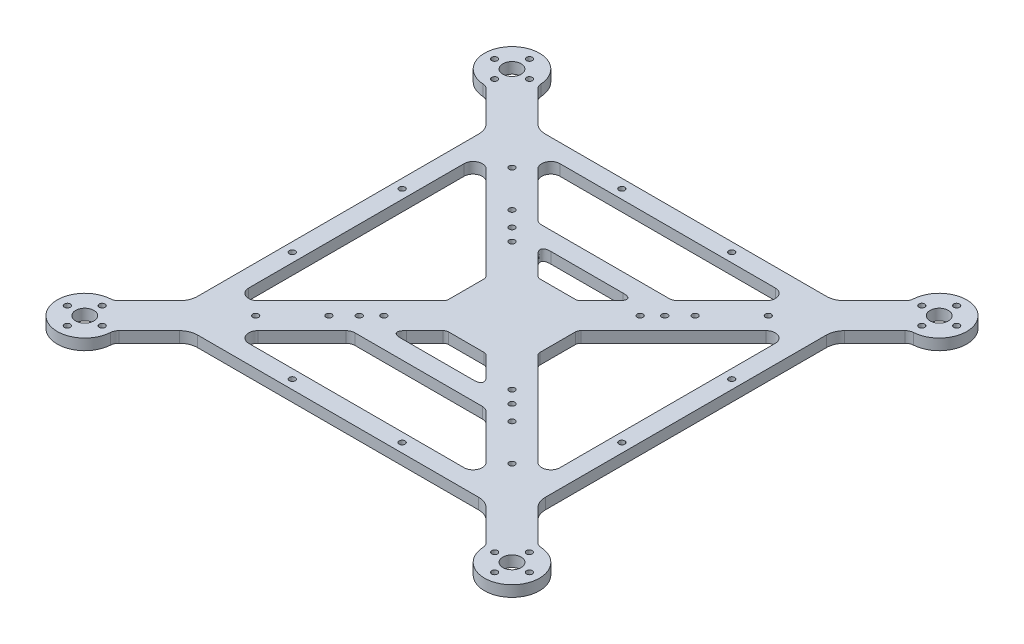
SolidWorks part; units mm, degrees
material "Thornel Mat VMA"
ref_plane "前视基准面" through (0, 0, 0) normal (0, 0, 1) x (1, 0, 0)
ref_plane "上视基准面" through (0, 0, 0) normal (0, 1, 0) x (1, 0, 0)
ref_plane "右视基准面" through (0, 0, 0) normal (1, 0, 0) x (0, 0, -1)
other "Configuration Table"
sketch "草图4" plane through (0, 0, 0) normal (0, 1, 0) x (1, 0, 0)
  line L0 (-115.838, 101.6959) -> (-97.9289, 83.7868)
  line L1 (-116.6726, -116.6726) -> (116.6726, -116.6726) construction
  line L2 (-116.6726, -116.6726) -> (-116.6726, 116.6726) construction
  line L3 (-116.6726, 116.6726) -> (116.6726, 116.6726) construction
  line L4 (116.6726, -116.6726) -> (116.6726, 116.6726) construction
  line L5 (-116.6726, -116.6726) -> (116.6726, 116.6726) construction
  line L6 (-116.6726, 116.6726) -> (116.6726, -116.6726) construction
  line L7 (-101.6959, 115.838) -> (-83.7868, 97.9289)
  line L8 (115.838, 101.6959) -> (97.9289, 83.7868)
  line L9 (101.6959, 115.838) -> (83.7868, 97.9289)
  line L10 (-95, 76.7157) -> (-95, -76.7157)
  line L11 (-85, 58.7868) -> (-85, -58.7868)
  line L12 (0, 0) -> (0, 141.074) construction
  line L13 (0, 0) -> (180.939, 0) construction
  line L14 (76.7157, 95) -> (-76.7157, 95)
  line L15 (58.7868, 85) -> (-58.7868, 85)
  line L16 (95, -76.7157) -> (95, 76.7157)
  line L17 (85, -58.7868) -> (85, 58.7868)
  line L18 (-76.7157, -95) -> (76.7157, -95)
  line L19 (-58.7868, -85) -> (58.7868, -85)
  line L20 (3.5355, -17.6777) -> (62.3223, -76.4645)
  line L21 (-62.3223, 76.4645) -> (-3.5355, 17.6777)
  line L22 (62.3223, 76.4645) -> (3.5355, 17.6777)
  line L23 (76.4645, 62.3223) -> (17.6777, 3.5355)
  line L24 (97.9289, -83.7868) -> (115.838, -101.6959)
  line L25 (83.7868, -97.9289) -> (101.6959, -115.838)
  line L26 (-83.7868, -97.9289) -> (-101.6959, -115.838)
  line L27 (-97.9289, -83.7868) -> (-115.838, -101.6959)
  line L28 (-17.6777, -3.5355) -> (-76.4645, -62.3223)
  line L29 (-3.5355, -17.6777) -> (-62.3223, -76.4645)
  line L30 (-76.4645, 62.3223) -> (-17.6777, 3.5355)
  line L31 (17.6777, -3.5355) -> (76.4645, -62.3223)
  circle A0 centre (-116.6726, 116.6726) radius 15
  circle A1 centre (-116.6726, 116.6726) radius 5
  circle A2 centre (-116.6726, 116.6726) radius 9.5 construction
  circle A3 centre (-116.6726, 126.1726) radius 1.6
  circle A4 centre (-107.1726, 116.6726) radius 1.6
  circle A5 centre (-116.6726, 107.1726) radius 1.6
  circle A6 centre (-126.1726, 116.6726) radius 1.6
  circle A7 centre (116.6726, 116.6726) radius 15
  circle A8 centre (116.6726, 116.6726) radius 5
  circle A9 centre (126.1726, 116.6726) radius 1.6
  circle A10 centre (116.6726, 107.1726) radius 1.6
  circle A11 centre (107.1726, 116.6726) radius 1.6
  circle A12 centre (116.6726, 126.1726) radius 1.6
  circle A13 centre (116.6726, 116.6726) radius 9.5 construction
  circle A14 centre (116.6726, -116.6726) radius 15
  circle A15 centre (116.6726, -116.6726) radius 5
  circle A16 centre (116.6726, -126.1726) radius 1.6
  circle A17 centre (107.1726, -116.6726) radius 1.6
  circle A18 centre (116.6726, -107.1726) radius 1.6
  circle A19 centre (126.1726, -116.6726) radius 1.6
  circle A20 centre (116.6726, -116.6726) radius 9.5 construction
  circle A21 centre (-116.6726, -116.6726) radius 15
  circle A22 centre (-116.6726, -116.6726) radius 5
  circle A23 centre (-126.1726, -116.6726) radius 1.6
  circle A24 centre (-116.6726, -107.1726) radius 1.6
  circle A25 centre (-107.1726, -116.6726) radius 1.6
  circle A26 centre (-116.6726, -126.1726) radius 1.6
  circle A27 centre (-116.6726, -116.6726) radius 9.5 construction
  arc A28 (-83.7868, 97.9289) -> (-76.7157, 95) centre (-76.7157, 105) ccw
  arc A29 (76.7157, 95) -> (83.7868, 97.9289) centre (76.7157, 105) ccw
  arc A30 (97.9289, 83.7868) -> (95, 76.7157) centre (105, 76.7157) ccw
  arc A31 (95, -76.7157) -> (97.9289, -83.7868) centre (105, -76.7157) ccw
  arc A32 (83.7868, -97.9289) -> (76.7157, -95) centre (76.7157, -105) ccw
  arc A33 (-76.7157, -95) -> (-83.7868, -97.9289) centre (-76.7157, -105) ccw
  arc A34 (-97.9289, -83.7868) -> (-95, -76.7157) centre (-105, -76.7157) ccw
  arc A35 (-95, 76.7157) -> (-97.9289, 83.7868) centre (-105, 76.7157) ccw
  arc A36 (-62.3223, -76.4645) -> (-58.7868, -85) centre (-58.7868, -80) ccw
  arc A37 (58.7868, -85) -> (62.3223, -76.4645) centre (58.7868, -80) ccw
  arc A38 (85, -58.7868) -> (76.4645, -62.3223) centre (80, -58.7868) cw
  arc A39 (76.4645, 62.3223) -> (85, 58.7868) centre (80, 58.7868) cw
  arc A40 (62.3223, 76.4645) -> (58.7868, 85) centre (58.7868, 80) ccw
  arc A41 (-62.3223, 76.4645) -> (-58.7868, 85) centre (-58.7868, 80) cw
  arc A42 (-76.4645, -62.3223) -> (-85, -58.7868) centre (-80, -58.7868) cw
  arc A43 (-85, 58.7868) -> (-76.4645, 62.3223) centre (-80, 58.7868) cw
  arc A44 (3.5355, -17.6777) -> (-3.5355, -17.6777) centre (0, -21.2132) ccw
  arc A45 (-17.6777, -3.5355) -> (-17.6777, 3.5355) centre (-21.2132, 0) ccw
  arc A46 (3.5355, 17.6777) -> (-3.5355, 17.6777) centre (0, 21.2132) cw
  arc A47 (17.6777, -3.5355) -> (17.6777, 3.5355) centre (21.2132, 0) cw
  point P0 (0, 0)
  point P20 (-116.6726, 116.6726)
  point P33 (116.6726, 116.6726)
  point P46 (116.6726, -116.6726)
  point P59 (-116.6726, -116.6726)
  point P60 (0, 0)
  point P69 (-95, 0)
  point P76 (-14.1421, 0)
  point P89 (0, 0)
  point P104 (-95, -80.8579)
  point P115 (85, 70.8579)
  point P118 (70.8579, 85)
  point P123 (-85, -70.8579)
  point P126 (-85, 70.8579)
  dimension "D2" = 30
  dimension "D3" = 10
  dimension "D4" = 19
  dimension "D5" = 3.2
  dimension "D14" = 10
  dimension "D15" = 5
  dimension "D16" = 5
  dimension "D17" = 5
  dimension "D18" = 5
  dimension "D19" = 5
  dimension "D1" = 330
  dimension "D8" = 20
  dimension "D9" = 20
  dimension "D10" = 10
  dimension "D11" = 190
  dimension "D12" = 190
  dimension "D13" = 10
  dimension "D6" = 4
  dimension "D7" = 4
extrude "凸台-拉伸2" add sketch "草图4" along normal blind 6 contours A35 L10 A34 L27 A21 L26 A33 L18 A32 L25 A14 L24 A31 L16 A30 L8 A7 L9 A29 L14 A28 L7 A0 L0 A45 L28 A42 L11 A43 L30 A44 L20 A37 L19 A36 L29 L22 A46 L21 A41 L15 A40 L31 A47 L23 A39 L17 | A0 A6 A5 A4 A3 A1 | A21 A26 A25 A24 A23 A22 | A14 A19 A18 A17 A16 A15 | A7 A12 A11 A10 A9 A8
sketch "草图6" plane through (0, 6, 0) normal (0, 1, 0) x (1, 0, 0)
  line L0 (-41, -26.8579) -> (-41, 26.8579)
  line L1 (-46, -29) -> (46, -29) construction
  line L2 (-46, -29) -> (-46, 29) construction
  line L3 (-46, 29) -> (46, 29) construction
  line L4 (46, -29) -> (46, 29) construction
  line L5 (-46, -29) -> (46, 29) construction
  line L6 (-46, 29) -> (46, -29) construction
  line L7 (-51, -36.8579) -> (-51, 36.8579)
  line L8 (-51, -29) -> (-51, 29) construction
  line L9 (-76.4645, 62.3223) -> (-17.6777, 3.5355) construction
  line L10 (-41, -29) -> (-41, 29) construction
  line L11 (-17.6777, -3.5355) -> (-76.4645, -62.3223) construction
  line L12 (-41, -26.8579) -> (-51, -36.8579)
  line L13 (-51, 36.8579) -> (-41, 26.8579)
  line L14 (0, 0) -> (0, 52.0097) construction
  line L15 (51, 36.8579) -> (41, 26.8579)
  line L16 (41, -26.8579) -> (51, -36.8579)
  line L17 (51, -36.8579) -> (51, 36.8579)
  line L18 (41, -26.8579) -> (41, 26.8579)
  line L19 (-26.8579, 41) -> (26.8579, 41)
  line L20 (25, -25) -> (-25, -25)
  line L21 (25, -25) -> (25, 25)
  line L22 (25, 25) -> (-25, 25)
  line L23 (-25, -25) -> (-25, 25)
  line L24 (25, -25) -> (-25, 25) construction
  line L25 (25, 25) -> (-25, -25) construction
  line L26 (-36.8579, 51) -> (36.8579, 51)
  line L27 (-26.8579, 41) -> (-36.8579, 51)
  line L28 (36.8579, 51) -> (26.8579, 41)
  line L29 (-29, 46) -> (29, 46) construction
  line L30 (36.8579, -51) -> (26.8579, -41)
  line L31 (-26.8579, -41) -> (-36.8579, -51)
  line L32 (-36.8579, -51) -> (36.8579, -51)
  line L33 (-26.8579, -41) -> (26.8579, -41)
  line L34 (-29, -46) -> (29, -46) construction
  line L35 (41, 26.8579) -> (41, -26.8579)
  line L36 (51, 36.8579) -> (51, -36.8579)
  line L37 (41, 26.8579) -> (51, 36.8579)
  line L38 (51, -36.8579) -> (41, -26.8579)
  line L39 (46, 29) -> (46, -29) construction
  line L40 (-51, -36.8579) -> (-41, -26.8579)
  line L41 (-41, 26.8579) -> (-51, 36.8579)
  line L42 (-51, 36.8579) -> (-51, -36.8579)
  line L43 (-41, 26.8579) -> (-41, -26.8579)
  line L44 (-46, 29) -> (-46, -29) construction
  line L45 (26.8579, -41) -> (-26.8579, -41)
  line L46 (36.8579, -51) -> (-36.8579, -51)
  line L47 (26.8579, -41) -> (36.8579, -51)
  line L48 (-36.8579, -51) -> (-26.8579, -41)
  line L49 (29, -46) -> (-29, -46) construction
  line L50 (-36.8579, 51) -> (-26.8579, 41)
  line L51 (26.8579, 41) -> (36.8579, 51)
  line L52 (36.8579, 51) -> (-36.8579, 51)
  line L53 (26.8579, 41) -> (-26.8579, 41)
  line L54 (29, 46) -> (-29, 46) construction
  point P0 (0, 0)
  point P67 (0, 0)
  dimension "D1" = 58
  dimension "D2" = 92
  dimension "D5" = 50
  dimension "D6" = 50
  dimension "D3" = 5
  dimension "D4" = 5
  dimension "D7" = 4
extrude "凸台-拉伸3" add sketch "草图6" against normal up to surface (6 mm away) contours L13 L7 L12 L0 | L18 L16 L17 L15 | L28 L26 L27 L19 | L33 L31 L32 L30 up to face at (-59.8637, 0, 0)
sketch "草图7" plane through (0, 6, 0) normal (0, 1, 0) x (1, 0, 0)
  line L1 (10, -10) -> (-10, -10) construction
  line L2 (10, -10) -> (10, 10) construction
  line L3 (10, 10) -> (-10, 10) construction
  line L4 (-10, -10) -> (-10, 10) construction
  line L5 (10, -10) -> (-10, 10) construction
  line L6 (10, 10) -> (-10, -10) construction
  line L7 (46, -29) -> (-46, -29) construction
  line L8 (46, -29) -> (46, 29) construction
  line L9 (46, 29) -> (-46, 29) construction
  line L10 (-46, -29) -> (-46, 29) construction
  line L11 (46, -29) -> (-46, 29) construction
  line L12 (46, 29) -> (-46, -29) construction
  circle A0 centre (-10, 10) radius 1.5
  circle A1 centre (10, 10) radius 1.5
  circle A2 centre (10, -10) radius 1.5
  circle A3 centre (-10, -10) radius 1.5
  circle A4 centre (-46, 29) radius 1.5
  circle A5 centre (46, 29) radius 1.5
  circle A6 centre (46, -29) radius 1.5
  circle A7 centre (-46, -29) radius 1.5
  point P0 (0, 0)
  point P2 (0, 0)
  point P16 (0, 0)
  dimension "D3" = 3
  dimension "D7" = 3
  dimension "D1" = 20
  dimension "D2" = 20
  dimension "D5" = 92
  dimension "D6" = 58
  dimension "D4" = 4
extrude "切除-拉伸1" [suppressed] cut sketch "草图7" against normal through all
fillet "圆角2" radius 3 8 edges at (41, 3, -26.8579) (41, 3, 26.8579) (-41, 3, 26.8579) (-41, 3, -26.8579) (26.8579, 3, 41) (-26.8579, 3, 41) (26.8579, 3, -41) (-26.8579, 3, -41)
fillet "圆角3" radius 5 8 edges at (51, 3, 36.8579) (51, 3, -36.8579) (-51, 3, 36.8579) (-51, 3, -36.8579) (-36.8579, 3, 51) (36.8579, 3, 51) (36.8579, 3, -51) (-36.8579, 3, -51)
fillet "圆角4" radius 5 8 edges at (101.6959, 3, -115.838) (115.838, 3, -101.6959) (115.838, 3, 101.6959) (101.6959, 3, 115.838) (-101.6959, 3, 115.838) (-115.838, 3, 101.6959) (-101.6959, 3, -115.838) (-115.838, 3, -101.6959)
sketch "草图8" plane through (0, 6, 0) normal (0, 1, 0) x (1, 0, 0)
  line L1 (20, -20) -> (-20, -20) construction
  line L2 (20, -20) -> (20, 20) construction
  line L3 (20, 20) -> (-20, 20) construction
  line L4 (-20, -20) -> (-20, 20) construction
  line L5 (20, -20) -> (-20, 20) construction
  line L6 (20, 20) -> (-20, -20) construction
  circle A0 centre (-20, 20) radius 1.5
  circle A1 centre (20, 20) radius 1.5
  circle A2 centre (20, -20) radius 1.5
  circle A3 centre (-20, -20) radius 1.5
  point P0 (0, 0)
  point P16 (0, 0)
  dimension "D3" = 3
  dimension "D1" = 40
  dimension "D2" = 40
  dimension "D4" = 4
extrude "切除-拉伸2" [suppressed] cut sketch "草图8" against normal through all
sketch "草图9" plane through (0, 6, 0) normal (0, 1, 0) x (1, 0, 0)
  line L1 (0, 0) -> (0, 15.1616) construction
  line L2 (0, 0) -> (18.0574, 0) construction
  line L3 (0, 0) -> (-35, 35) construction
  circle A0 centre (-35, 35) radius 1.6
  circle A3 centre (35, 35) radius 1.6
  circle A4 centre (-35, -35) radius 1.6
  circle A5 centre (35, -35) radius 1.6
  dimension "D2" = 3.2
  dimension "D1" = 45
  dimension "D3" = 70
extrude "切除-拉伸3" cut sketch "草图9" against normal through all
sketch "草图10" [suppressed] plane through (0, 6, 0) normal (0, 1, 0) x (1, 0, 0)
  circle A0 centre (-46, 29) radius 1.5 construction
  circle A1 centre (-46, 29) radius 1.5
  circle A2 centre (46, 29) radius 1.5 construction
  circle A3 centre (46, 29) radius 1.5
  circle A4 centre (-46, -29) radius 1.5 construction
  circle A5 centre (-46, -29) radius 1.5
  circle A6 centre (46, -29) radius 1.5 construction
  circle A7 centre (46, -29) radius 1.5
extrude "凸台-拉伸4" [suppressed] add sketch "草图10" against normal up to surface (6 mm away)
sketch "草图11" plane through (0, 6, 0) normal (0, 1, 0) x (1, 0, 0)
  line L1 (27.5, -27.5) -> (-27.5, -27.5) construction
  line L2 (27.5, -27.5) -> (27.5, 27.5) construction
  line L3 (27.5, 27.5) -> (-27.5, 27.5) construction
  line L4 (-27.5, -27.5) -> (-27.5, 27.5) construction
  line L5 (27.5, -27.5) -> (-27.5, 27.5) construction
  line L6 (27.5, 27.5) -> (-27.5, -27.5) construction
  circle A0 centre (-27.5, 27.5) radius 1.6
  circle A1 centre (27.5, 27.5) radius 1.6
  circle A2 centre (27.5, -27.5) radius 1.6
  circle A3 centre (-27.5, -27.5) radius 1.6
  point P0 (0, 0)
  point P16 (0, 0)
  dimension "D3" = 3.2
  dimension "D1" = 55
  dimension "D4" = 4
extrude "切除-拉伸4" [suppressed] cut sketch "草图11" against normal through all
sketch "草图12" plane through (0, 6, 0) normal (0, 1, 0) x (1, 0, 0)
  line L0 (-35.8787, 21.7365) -> (-52.4645, 38.3223)
  line L1 (-35.8787, -21.7365) -> (-52.4645, -38.3223)
  line L2 (-41, -19.6152) -> (-41, 19.6152) construction
  line L3 (-51, -34.7868) -> (-51, 34.7868) construction
  line L4 (-41, -19.6152) -> (-41, 19.6152)
  line L5 (-51, -34.7868) -> (-51, 34.7868)
  line L6 (0, 0) -> (0, 23.6826) construction
  line L7 (51, -34.7868) -> (51, 34.7868)
  line L8 (41, -19.6152) -> (41, 19.6152)
  line L9 (35.8787, -21.7365) -> (52.4645, -38.3223)
  line L10 (35.8787, 21.7365) -> (52.4645, 38.3223)
  arc A0 (-52.4645, -38.3223) -> (-51, -34.7868) centre (-56, -34.7868) ccw construction
  arc A1 (-51, 34.7868) -> (-52.4645, 38.3223) centre (-56, 34.7868) ccw construction
  arc A2 (-52.4645, -38.3223) -> (-51, -34.7868) centre (-56, -34.7868) ccw
  arc A3 (-51, 34.7868) -> (-52.4645, 38.3223) centre (-56, 34.7868) ccw
  arc A4 (51, 34.7868) -> (52.4645, 38.3223) centre (56, 34.7868) cw
  arc A5 (52.4645, -38.3223) -> (51, -34.7868) centre (56, -34.7868) cw
  spline S0 degree 2 poles (117.6067, -1974.0441) (-43.0823, -8.6989) (-40.9727, 20.7023) (-40.9301, 21.2952) (-40.8081, 21.7781) (-40.6594, 22.3663) (-40.4006, 22.7849) (-40.0718, 23.3164) (-39.6048, 23.5072) (-39.1393, 23.6973) (-38.5319, 23.5511) (-38.0543, 23.4362) (-37.5355, 23.1253) (-37.1113, 22.8711) (-36.6658, 22.4851) (-14.4014, 3.1962) (1261.9746, -1499.9408) knots -9.521184 -9.521184 -9.521184 0.125 0.125 0.25 0.25 0.375 0.375 0.5 0.5 0.625 0.625 0.75 0.75 0.875 0.875 10.526415 10.526415 10.526415 only from (-41, 19.6152) to (-35.8787, 21.7365) construction
  spline S1 degree 2 poles (1261.6995, 1500.1454) (-14.3852, -3.1878) (-36.6667, -22.4859) (-37.116, -22.875) (-37.5437, -23.1302) (-38.0648, -23.4411) (-38.5438, -23.554) (-39.1522, -23.6973) (-39.6173, -23.502) (-40.0809, -23.3073) (-40.407, -22.7744) (-40.6634, -22.3554) (-40.8105, -21.7687) (-40.9306, -21.2891) (-40.9728, -20.7011) (-43.0767, 8.6815) (117.2676, 1974.094) knots -9.521184 -9.521184 -9.521184 0.125 0.125 0.25 0.25 0.375 0.375 0.5 0.5 0.625 0.625 0.75 0.75 0.875 0.875 10.526415 10.526415 10.526415 only from (-35.8787, -21.7365) to (-41, -19.6152) construction
  spline S2 degree 2 poles (-41, 19.6152) (-41, 20.3213) (-40.9727, 20.7023) (-40.9301, 21.2952) (-40.8081, 21.7781) (-40.6594, 22.3663) (-40.4006, 22.7849) (-40.0718, 23.3164) (-39.6048, 23.5072) (-39.1393, 23.6973) (-38.5319, 23.5511) (-38.0543, 23.4362) (-37.5355, 23.1253) (-37.1113, 22.8711) (-36.6658, 22.4851) (-36.3774, 22.2353) (-35.8787, 21.7365) knots 0 0 0 0.125 0.125 0.25 0.25 0.375 0.375 0.5 0.5 0.625 0.625 0.75 0.75 0.875 0.875 1 1 1
  spline S3 degree 2 poles (-35.8787, -21.7365) (-36.378, -22.2358) (-36.6667, -22.4859) (-37.116, -22.875) (-37.5437, -23.1302) (-38.0648, -23.4411) (-38.5438, -23.554) (-39.1522, -23.6973) (-39.6173, -23.502) (-40.0809, -23.3073) (-40.407, -22.7744) (-40.6634, -22.3554) (-40.8105, -21.7687) (-40.9306, -21.2891) (-40.9728, -20.7011) (-41, -20.3205) (-41, -19.6152) knots 0 0 0 0.125 0.125 0.25 0.25 0.375 0.375 0.5 0.5 0.625 0.625 0.75 0.75 0.875 0.875 1 1 1
  spline S4 degree 2 poles (35.8787, -21.7365) (36.378, -22.2358) (36.6667, -22.4859) (37.116, -22.875) (37.5437, -23.1302) (38.0648, -23.4411) (38.5438, -23.554) (39.1522, -23.6973) (39.6173, -23.502) (40.0809, -23.3073) (40.407, -22.7744) (40.6634, -22.3554) (40.8105, -21.7687) (40.9306, -21.2891) (40.9728, -20.7011) (41, -20.3205) (41, -19.6152) knots 0 0 0 0.125 0.125 0.25 0.25 0.375 0.375 0.5 0.5 0.625 0.625 0.75 0.75 0.875 0.875 1 1 1
  spline S5 degree 2 poles (41, 19.6152) (41, 20.3213) (40.9727, 20.7023) (40.9301, 21.2952) (40.8081, 21.7781) (40.6594, 22.3663) (40.4006, 22.7849) (40.0718, 23.3164) (39.6048, 23.5072) (39.1393, 23.6973) (38.5319, 23.5511) (38.0543, 23.4362) (37.5355, 23.1253) (37.1113, 22.8711) (36.6658, 22.4851) (36.3774, 22.2353) (35.8787, 21.7365) knots 0 0 0 0.125 0.125 0.25 0.25 0.375 0.375 0.5 0.5 0.625 0.625 0.75 0.75 0.875 0.875 1 1 1
extrude "切除-拉伸5" cut sketch "草图12" against normal through all
sketch "草图13" plane through (0, 6, 0) normal (0, 1, 0) x (1, 0, 0)
  line L1 (-25, -25) -> (25, -25)
  line L2 (-25, -25) -> (-25, 25)
  line L3 (-25, 25) -> (25, 25)
  line L4 (25, -25) -> (25, 25)
  line L5 (-25, -25) -> (25, 25) construction
  line L6 (-25, 25) -> (25, -25) construction
  point P0 (0, 0)
  dimension "D1" = 50
  dimension "D2" = 50
extrude "凸台-拉伸5" add sketch "草图13" against normal up to surface (6 mm away) up to face at (35, 0, -33.4)
fillet "圆角5" radius 3 8 edges at (-10.8579, 3, -25) (10.8579, 3, -25) (25, 3, -10.8579) (25, 3, 10.8579) (10.8579, 3, 25) (-10.8579, 3, 25) (-25, 3, 10.8579) (-25, 3, -10.8579)
sketch "草图14" plane through (0, 6, 0) normal (0, 1, 0) x (1, 0, 0)
  line L1 (50, -50) -> (-50, -50) construction
  line L2 (50, -50) -> (50, 50) construction
  line L3 (50, 50) -> (-50, 50) construction
  line L4 (-50, -50) -> (-50, 50) construction
  line L5 (50, -50) -> (-50, 50) construction
  line L6 (50, 50) -> (-50, -50) construction
  circle A0 centre (-50, 50) radius 1.6
  circle A1 centre (50, 50) radius 1.6
  circle A2 centre (50, -50) radius 1.6
  circle A3 centre (-50, -50) radius 1.6
  point P0 (0, 0)
  point P16 (0, 0)
  dimension "D2" = 3.2
  dimension "D1" = 100
  dimension "D3" = 4
extrude "切除-拉伸6" cut sketch "草图14" against normal through all
sketch "草图15" plane through (0, 6, 0) normal (0, 1, 0) x (1, 0, 0)
  line L1 (30, -90) -> (-30, -90) construction
  line L2 (30, -90) -> (30, 90) construction
  line L3 (30, 90) -> (-30, 90) construction
  line L4 (-30, -90) -> (-30, 90) construction
  line L5 (30, -90) -> (-30, 90) construction
  line L6 (30, 90) -> (-30, -90) construction
  circle A0 centre (-30, 90) radius 1.6
  circle A1 centre (30, 90) radius 1.6
  circle A4 centre (90, 30) radius 1.6
  circle A5 centre (30, -90) radius 1.6
  circle A6 centre (-90, -30) radius 1.6
  circle A7 centre (90, -30) radius 1.6
  circle A8 centre (-30, -90) radius 1.6
  circle A9 centre (-90, 30) radius 1.6
  point P0 (0, 0)
  point P17 (0, 0)
  point P23 (0, 0)
  dimension "D3" = 3.2
  dimension "D1" = 180
  dimension "D2" = 60
  dimension "D4" = 4
  dimension "D5" = 4
extrude "切除-拉伸7" cut sketch "草图15" against normal through all
sketch "草图16" plane through (0, 6, 0) normal (0, 1, 0) x (1, 0, 0)
  line L1 (70, -70) -> (-70, -70) construction
  line L2 (70, -70) -> (70, 70) construction
  line L3 (70, 70) -> (-70, 70) construction
  line L4 (-70, -70) -> (-70, 70) construction
  line L5 (70, -70) -> (-70, 70) construction
  line L6 (70, 70) -> (-70, -70) construction
  circle A0 centre (-70, 70) radius 1.6
  circle A1 centre (70, 70) radius 1.6
  circle A2 centre (70, -70) radius 1.6
  circle A3 centre (-70, -70) radius 1.6
  point P0 (0, 0)
  dimension "D2" = 3.2
  dimension "D1" = 140
extrude "切除-拉伸8" cut sketch "草图16" against normal through all
sketch "草图17" plane through (0, 6, 0) normal (0, 1, 0) x (1, 0, 0)
  line L1 (41.7157, -41.7157) -> (-41.7157, -41.7157) construction
  line L2 (41.7157, -41.7157) -> (41.7157, 41.7157) construction
  line L3 (41.7157, 41.7157) -> (-41.7157, 41.7157) construction
  line L4 (-41.7157, -41.7157) -> (-41.7157, 41.7157) construction
  line L5 (41.7157, -41.7157) -> (-41.7157, 41.7157) construction
  line L6 (41.7157, 41.7157) -> (-41.7157, -41.7157) construction
  circle A0 centre (-41.7157, 41.7157) radius 1.6
  circle A1 centre (41.7157, 41.7157) radius 1.6
  circle A2 centre (41.7157, -41.7157) radius 1.6
  circle A3 centre (-41.7157, -41.7157) radius 1.6
  circle A4 centre (-70, 70) radius 1.6 construction
  point P0 (0, 0)
  dimension "D1" = 40
  dimension "D2" = 3.2
extrude "切除-拉伸9" cut sketch "草图17" against normal through all
